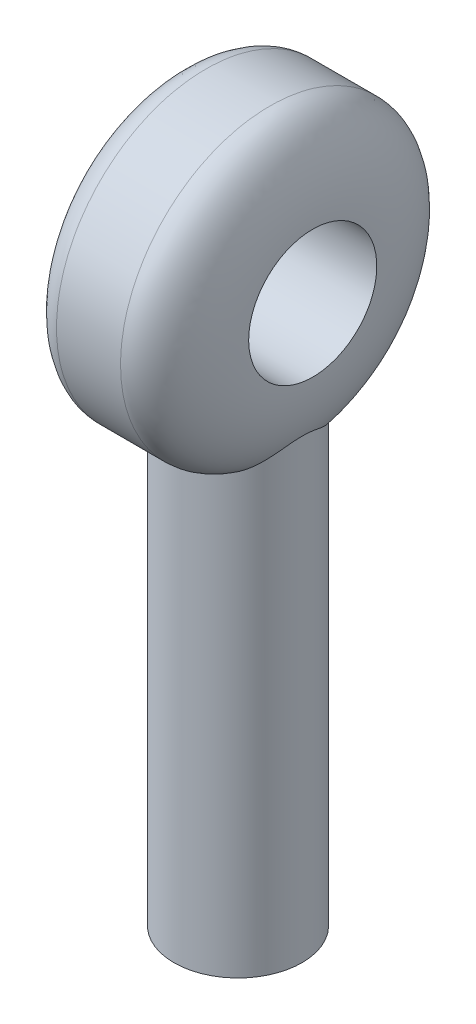
SolidWorks part; units mm, degrees
ref_plane "Płaszczyzna przednia" through (0, 0, 0) normal (0, 0, 1) x (1, 0, 0)
ref_plane "Płaszczyzna górna" through (0, 0, 0) normal (0, 1, 0) x (1, 0, 0)
ref_plane "Płaszczyzna prawa" through (0, 0, 0) normal (1, 0, 0) x (0, 0, -1)
sketch "Szkic1" plane through (0, 0, 0) normal (0, 0, 1) x (1, 0, 0)
  line L0 (0, 0) -> (7, 0)
  line L1 (7, 0) -> (7, 4)
  line L2 (0, 0) -> (0, 4)
  line L3 (0, -3) -> (7, -3) construction
  line L4 (0, 4) -> (7, 4)
  dimension "D1" = 7
  dimension "D2" = 3
  dimension "D3" = 7
revolve "Obrót1" add sketch "Szkic1" angle 360 about L3
ref_plane "Płaszczyzna1" through (0, -10, 0) normal (0, 1, 0) x (1, 0, 0)
sketch "Szkic2" plane through (0, -10, 0) normal (0, 1, 0) x (1, 0, 0)
  line L0 (3.5, 7) -> (3.5, -7) construction
  line L1 (7, 7) -> (0, 7) construction
  line L2 (0, -7) -> (7, -7) construction
  line L3 (7, 0) -> (0, 0) construction
  line L4 (7, -7) -> (7, 7) construction
  circle A0 centre (3.5, 0) radius 3
extrude "Dodanie-wyciągnięcie1" add sketch "Szkic2" against normal blind 20 and the other way up to surface other way up to face at (0, -3, 7)
fillet "Zaokrąglenie1" radius 2 2 edges at (7, -3, 7) (0, -3, 7) second distance 4 first distance on face at (3.9084, -9.3377, 2.9721)
